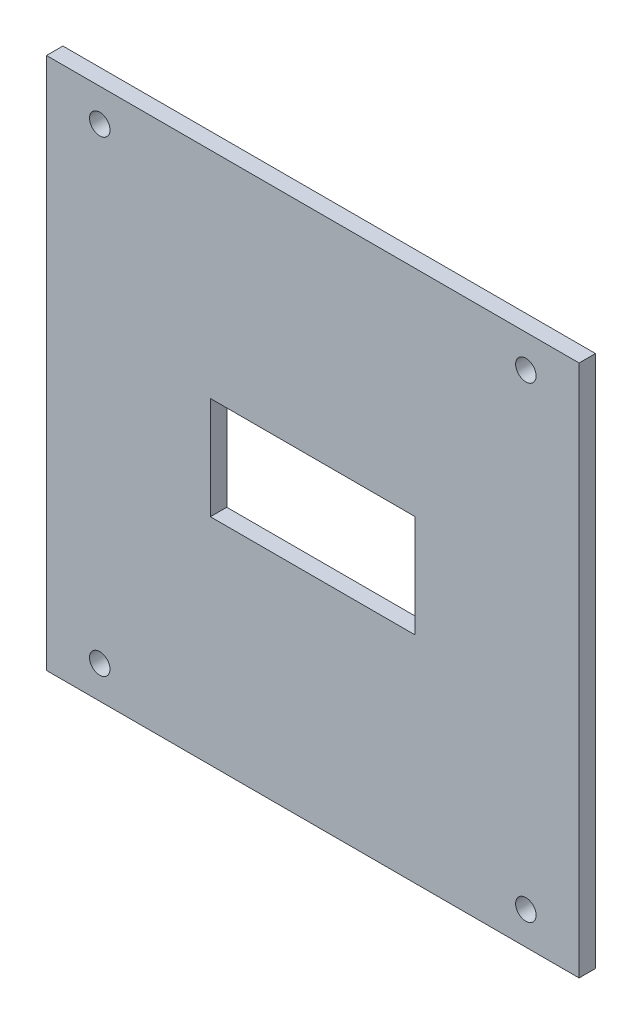
SolidWorks part; units mm, degrees
material "Aluminum"
ref_plane "Front Plane" through (0, 0, 0) normal (0, 0, 1) x (1, 0, 0)
ref_plane "Top Plane" through (0, 0, 0) normal (0, 1, 0) x (1, 0, 0)
ref_plane "Right Plane" through (0, 0, 0) normal (1, 0, 0) x (0, 0, -1)
sketch "Sketch1" plane through (0, 0, 0) normal (0, 0, 1) x (1, 0, 0)
  line L1 (65, -65) -> (-65, -65)
  line L2 (65, -65) -> (65, 65)
  line L3 (65, 65) -> (-65, 65)
  line L4 (-65, -65) -> (-65, 65)
  line L5 (65, -65) -> (-65, 65) construction
  line L6 (65, 65) -> (-65, -65) construction
  point P0 (0, 0)
  dimension "D1" = 130
  dimension "D2" = 130
extrude "Boss-Extrude1" add sketch "Sketch1" along normal blind 2 and the other way blind 2
hole_wizard "Tap Drill for M5x0.8 Tap1" positions "Sketch3" profile "Sketch2" hole size "M5x0.8" standard "ANSI Metric" end condition through all
sketch "Sketch3" plane through (0, 0, -2) normal (0, 0, -1) x (-1, 0, 0)
  point P0 (-52, 57)
  point P3 (52, 57)
  point P6 (52, -57)
  point P9 (-52, -57)
sketch "Sketch2" plane through (52, 57, -2) normal (1, 0, 0) x (0, 1, 0)
  line L0 (0, 0) -> (0, 4)
  line L1 (0, 4) -> (2.5, 4)
  line L2 (2.5, 4) -> (2.5, 0)
  line L5 (2.5, 0) -> (0, 0)
  line L11 (0, -6.35) -> (0, 107.95) construction
  dimension "Thru Hole Dia." = 5
  dimension "Thru Hole Depth" = 4
sketch "Sketch5" plane through (0, 0, -2) normal (0, 0, -1) x (-1, 0, 0)
  line L1 (25, -12.5) -> (-25, -12.5)
  line L2 (25, -12.5) -> (25, 12.5)
  line L3 (25, 12.5) -> (-25, 12.5)
  line L4 (-25, -12.5) -> (-25, 12.5)
  line L5 (25, -12.5) -> (-25, 12.5) construction
  line L6 (25, 12.5) -> (-25, -12.5) construction
  point P0 (0, 0)
  dimension "D1" = 50
  dimension "D2" = 25
extrude "Cut-Extrude2" cut sketch "Sketch5" against normal blind 20
